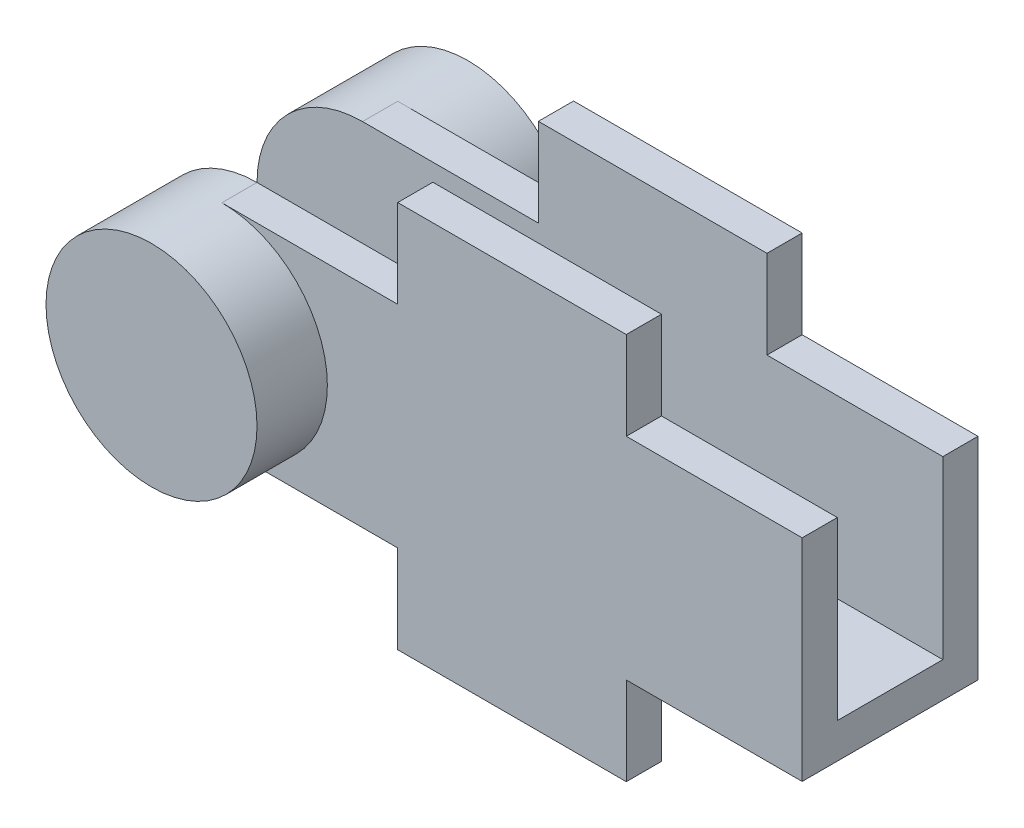
SolidWorks part; units mm, degrees
ref_plane "Front Plane" through (0, 0, 0) normal (0, 0, 1) x (1, 0, 0)
ref_plane "Top Plane" through (0, 0, 0) normal (0, 1, 0) x (1, 0, 0)
ref_plane "Right Plane" through (0, 0, 0) normal (1, 0, 0) x (0, 0, -1)
sketch "Sketch1" plane through (0, 0, 0) normal (0, 0, 1) x (1, 0, 0)
  line L0 (0, 0) -> (-215, 0) construction
  line L1 (-215, 30) -> (-165, 30)
  line L2 (-165, 30) -> (-165, 55.061)
  line L3 (-165, 55.061) -> (-100, 55.061)
  line L4 (-100, 55.061) -> (-100, 30)
  line L5 (-215, 40.0631) -> (-215, -32.0703) construction
  line L6 (-100, 30) -> (-50, 30)
  line L7 (-50, 30) -> (-50, -32.0703)
  line L8 (-100, -30) -> (-50, -30)
  line L9 (-100, -55.061) -> (-100, -30)
  line L10 (-165, -30) -> (-165, -55.061)
  line L11 (-165, -55.061) -> (-100, -55.061)
  line L12 (-215, -30) -> (-165, -30)
  arc A0 (-215, 30) -> (-215, -30) centre (-215, 0) ccw
  dimension "D2" = 50
  dimension "D1" = 215
  dimension "D3" = 50
  dimension "D4" = 50
extrude "Boss-Extrude1" add sketch "Sketch1" along normal blind 10 contours L1 A0 L12 L10 L11 L9 L8 L7 L6 L4 L3 L2 region at (-141.7393, 0, 0)
sketch "Sketch2" plane through (0, 0, 10) normal (0, 0, 1) x (1, 0, 0)
  circle A0 centre (-215, 0) radius 30
extrude "Boss-Extrude2" add sketch "Sketch2" along normal blind 20
sketch "Sketch3" plane through (0, -30, 0) normal (0, -1, 0) x (1, 0, 0)
  line L0 (-215, 10) -> (-215, 0) construction
  line L1 (-215, 10) -> (-50, 10)
  line L2 (-215, 10) -> (-215, -40)
  line L3 (-215, -40) -> (-50, -40)
  line L4 (-50, 10) -> (-50, -40)
  line L5 (-100, 0) -> (-50, 0) construction
  dimension "D1" = 50
  dimension "D2" = 10
extrude "Boss-Extrude3" add sketch "Sketch3" against normal blind 10
ref_plane "Plane5" through (0, 0, -15) normal (0, 0, 1) x (1, 0, 0)
mirror "Mirror1" about plane through (0, 0, -15) normal (0, 0, 1) of "Boss-Extrude2", "Boss-Extrude1"
